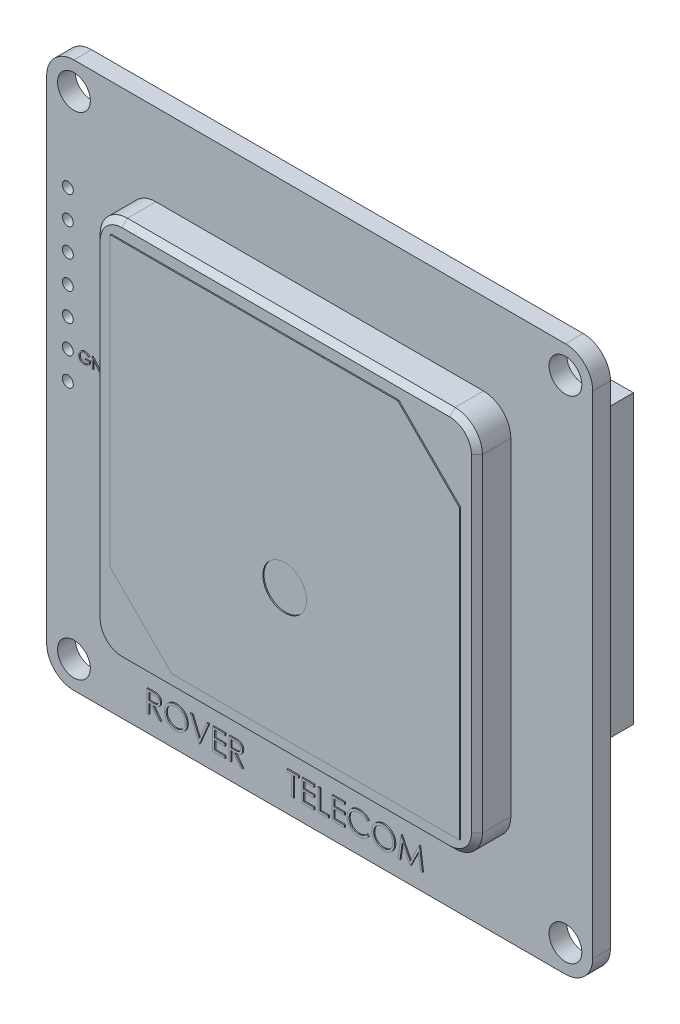
SolidWorks part; units mm, degrees
ref_plane "Ebene vorne" through (0, 0, 0) normal (0, 0, 1) x (1, 0, 0)
ref_plane "Ebene oben" through (0, 0, 0) normal (0, 1, 0) x (1, 0, 0)
ref_plane "Ebene rechts" through (0, 0, 0) normal (1, 0, 0) x (0, 0, -1)
sketch "Sketch1" plane through (0, 0, 0) normal (0, 0, 1) x (1, 0, 0)
  line L0 (25, 25) -> (-25, 25)
  line L1 (-25, 25) -> (-25, -25)
  line L2 (-25, -25) -> (25, -25)
  line L3 (25, -25) -> (25, 25)
  line L4 (-25, 0) -> (25, 0) construction
  line L5 (0, 25) -> (0, -25) construction
  dimension "D1" = 50
  dimension "D2" = 50
extrude "Boss-Extrude1" add sketch "Sketch1" against normal blind 1.62
sketch "Sketch2" plane through (0, 0, 0) normal (0, 0, 1) x (1, 0, 0)
  line L0 (-17.5, 17.5) -> (17.5, 17.5)
  line L1 (17.5, 17.5) -> (17.5, -17.5)
  line L2 (17.5, -17.5) -> (-17.5, -17.5)
  line L3 (-17.5, -17.5) -> (-17.5, 17.5)
  line L4 (0, -17.5) -> (0, 17.5) construction
  line L5 (-17.5, 0) -> (17.5, 0) construction
  dimension "D1" = 35
  dimension "D2" = 35
extrude "Boss-Extrude2" add sketch "Sketch2" along normal blind 3.1
sketch "Sketch3" plane through (0, 0, 3.1) normal (0, 0, 1) x (1, 0, 0)
  line L0 (16, -16) -> (-16, -16)
  line L1 (-16, -16) -> (-16, 16)
  line L2 (-16, 16) -> (16, 16)
  line L3 (16, 16) -> (16, -16)
extrude "Boss-Extrude3" add sketch "Sketch3" along normal blind 0.1
hole_wizard "Ø3.0 (3) Diameter Hole1" positions "Sketch5" profile "Sketch4" hole size "Ø3.0" standard "ANSI Metric" end condition through all
sketch "Sketch5" plane through (0, 0, 0) normal (0, 0, 1) x (1, 0, 0)
  point P0 (22.5, -22.5)
  point P1 (-22.5, 22.5)
  point P2 (22.5, 22.5)
  point P3 (-22.5, -22.5)
sketch "Sketch4" plane through (22.5, -22.5, 0) normal (1, 0, 0) x (0, -1, 0)
  line L0 (0, 0) -> (0, 1.62)
  line L1 (0, 1.62) -> (1.5, 1.62)
  line L2 (1.5, 1.62) -> (1.5, 0)
  line L5 (1.5, 0) -> (0, 0)
  line L11 (0, -6.35) -> (0, 107.95) construction
  dimension "Thru Hole Dia." = 3
  dimension "Thru Hole Depth" = 1.62
hole_wizard "Ø4.0 (4) Diameter Hole1" positions "Sketch7" profile "Sketch6" hole size "Ø4.0" standard "ANSI Metric"
sketch "Sketch7" plane through (0, 0, 3.2) normal (0, 0, 1) x (1, 0, 0)
  point P0 (0, -4)
sketch "Sketch6" plane through (0, -4, 3.2) normal (1, 0, 0) x (0, -1, 0)
  line L0 (0, 0) -> (0, 0.1)
  line L1 (0, 0.1) -> (2, 0.1)
  line L2 (2, 0.1) -> (2, 0)
  line L5 (2, 0) -> (0, 0)
  line L10 (0, 0.1) -> (-2, 0.1) construction
  line L11 (0, -6.35) -> (0, 107.95) construction
  dimension "Hole Dia." = 4
  dimension "Hole Depth" = 0.1
  dimension "Drill Angle" = 180
fillet "Fillet1" radius 2.5 8 edges at (25, -25, -0.81) (25, 25, -0.81) (-25, -25, -0.81) (-25, 25, -0.81) (17.5, -17.5, 1.55) (17.5, 17.5, 1.55) (-17.5, -17.5, 1.55) (-17.5, 17.5, 1.55) tangent propagation no
chamfer "Chamfer1" distance 5.6569 angle 45 2 edges at (-16, -16, 3.15) (16, 16, 3.15)
chamfer "Chamfer2" distance 0.5 angle 45 8 edges at (17.5, 0, 3.1) (16.7678, -16.7678, 3.1) (16.7678, 16.7678, 3.1) (0, -17.5, 3.1) (0, 17.5, 3.1) (-16.7678, -16.7678, 3.1) (-16.7678, 16.7678, 3.1) (-17.5, 0, 3.1)
sketch "Sketch8" plane through (0, 0, -1.62) normal (0, 0, -1) x (-1, 0, 0)
  line L1 (-22, 17.5) -> (4.3, 17.5)
  line L2 (-22, 17.5) -> (-22, -8.8)
  line L3 (-22, -8.8) -> (4.3, -8.8)
  line L4 (4.3, 17.5) -> (4.3, -8.8)
  line L5 (-22.5, 25) -> (22.5, 25) construction
  line L6 (-25, -22.5) -> (-25, 22.5) construction
  dimension "D3" = 7.5
  dimension "D1" = 26.3
  dimension "D2" = 26.3
  dimension "D4" = 3
extrude "Boss-Extrude4" add sketch "Sketch8" along normal blind 5.1
sketch "Sketch9" plane through (0, 0, -1.62) normal (0, 0, -1) x (-1, 0, 0)
  line L0 (22.5, -25) -> (-22.5, -25) construction
  line L1 (-5.96, -19.2) -> (4.78, -19.2)
  line L2 (-5.96, -19.2) -> (-5.96, -25)
  line L3 (-5.96, -25) -> (4.78, -25)
  line L4 (4.78, -19.2) -> (4.78, -25)
  line L5 (-25, -22.5) -> (-25, 22.5) construction
  line L6 (5.98, -19.2) -> (16.72, -19.2)
  line L7 (5.98, -19.2) -> (5.98, -25)
  line L8 (5.98, -25) -> (16.72, -25)
  line L9 (16.72, -19.2) -> (16.72, -25)
  line L10 (-17, -20.6) -> (-9.46, -20.6)
  line L11 (-17, -20.6) -> (-17, -26.2)
  line L12 (-17, -26.2) -> (-9.46, -26.2)
  line L13 (-9.46, -20.6) -> (-9.46, -26.2)
  dimension "D1" = 1.2
  dimension "D2" = 5.6
  dimension "D3" = 7.54
  dimension "D4" = 8
  dimension "D5" = 3.5
  dimension "D6" = 5.8
  dimension "D7" = 10.74
  dimension "D8" = 10.74
  dimension "D9" = 1.2
extrude "Boss-Extrude5" add sketch "Sketch9" along normal blind 4.3 contours L1 L4 L3 L2 | L6 L9 L8 L7
extrude "Boss-Extrude6" add sketch "Sketch9<3>" along normal blind 2.62 contours L10 L13 L12 L11
sketch "Sketch9<3>" plane through (0, 0, -1.62) normal (0, 0, -1) x (-1, 0, 0) same geometry as "Sketch9"
sketch "Sketch10" plane through (0, 0, 0) normal (0, 0, 1) x (1, 0, 0)
  line L0 (-25, 22.5) -> (-25, -22.5) construction
  circle A0 centre (-23.06, 14.6) radius 0.5
  circle A1 centre (-23.06, 12.04) radius 0.5
  circle A2 centre (-23.06, 9.48) radius 0.5
  circle A3 centre (-23.06, 6.92) radius 0.5
  circle A4 centre (-23.06, 4.36) radius 0.5
  circle A5 centre (-23.06, 1.8) radius 0.5
  circle A6 centre (-23.06, -0.76) radius 0.5
  dimension "D1" = 1
  dimension "D2" = 1.94
  dimension "D3" = 10.4
  dimension "D4" = 7
extrude "Cut-Extrude1" cut sketch "Sketch10" against normal through all both and the other way through all
sketch "Sketch11" plane through (0, 0, 0) normal (0, 0, 1) x (1, 0, 0)
  text T0 "GND" font "Century Gothic" height 1
extrude "Boss-Extrude7" add sketch "Sketch11" along normal blind 0.1
sketch "Sketch12" plane through (0, 0, 0) normal (0, 0, 1) x (1, 0, 0)
  text T0 "ROVER     TELECOM" font "Century Gothic" height 2
extrude "Boss-Extrude8" add sketch "Sketch12" along normal blind 0.1
sketch "Sketch13" plane through (0, 0, 0) normal (0, 0, 1) x (1, 0, 0)
  circle A0 centre (22.5, -22.5) radius 1.5867
  circle A1 centre (22.5, -22.5) radius 1.5 construction
sketch "Sketch14" plane through (0, 0, 0) normal (0, 0, 1) x (1, 0, 0)
  circle A0 centre (22.5, 22.5) radius 1.5
  circle A1 centre (-22.5, 22.5) radius 1.5
  circle A2 centre (-22.5, -22.5) radius 1.5
  circle A3 centre (-22.5, -22.5) radius 1.5 construction
  circle A5 centre (22.5, 22.5) radius 1.5 construction
  circle A6 centre (-22.5, 22.5) radius 1.5 construction
